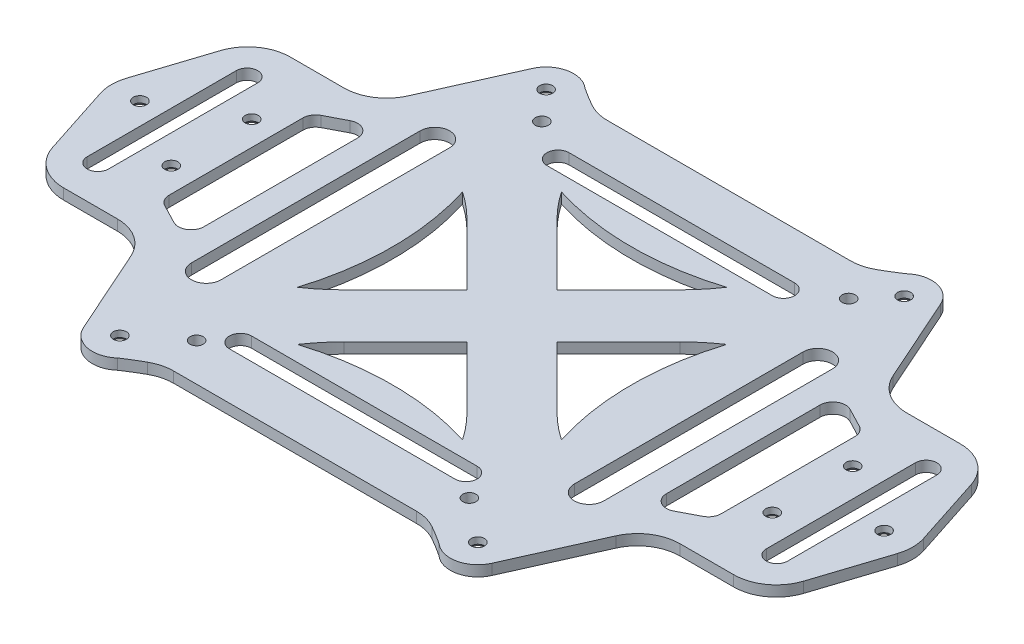
SolidWorks part; units mm, degrees
material "PPS"
ref_plane "前视基准面" through (0, 0, 0) normal (0, 0, 1) x (1, 0, 0)
ref_plane "上视基准面" through (0, 0, 0) normal (0, 1, 0) x (1, 0, 0)
ref_plane "右视基准面" through (0, 0, 0) normal (1, 0, 0) x (0, 0, -1)
sketch "参考" plane through (0, 0, 0) normal (0, 1, 0) x (1, 0, 0)
  line L3 (-133.7177, 0) -> (146.3754, 0) construction
  line L56 (0, 96.0639) -> (0, -115.1457) construction
  line L177 (114.5911, 7.4683) -> (114.5911, -7.4683)
  line L178 (114.5911, 7.4683) -> (43.1936, 17.6463)
  line L179 (114.5911, -7.4683) -> (43.1936, -17.6463)
  line L180 (-114.5911, -7.4683) -> (-43.1936, -17.6463)
  line L181 (-114.5911, 7.4683) -> (-114.5911, -7.4683)
  line L182 (-114.5911, 7.4683) -> (-43.1936, 17.6463)
  arc A18 (-37.7098, 54.831) -> (37.7098, 54.831) centre (0, 111.5317) ccw
  arc A20 (48.2756, 48.4632) -> (43.1936, 17.6463) centre (246.1791, 0) ccw
  arc A21 (48.2756, 48.4632) -> (37.7098, 54.831) centre (42, 50) ccw
  arc A22 (-37.7098, -54.831) -> (37.7098, -54.831) centre (0, -111.5317) cw
  arc A23 (48.2756, -48.4632) -> (43.1936, -17.6463) centre (246.1791, 0) cw
  arc A24 (48.2756, -48.4632) -> (37.7098, -54.831) centre (42, -50) cw
  arc A26 (-48.2756, -48.4632) -> (-37.7098, -54.831) centre (-42, -50) ccw
  arc A27 (-48.2756, -48.4632) -> (-43.1936, -17.6463) centre (-246.1791, 0) ccw
  arc A28 (-48.2756, 48.4632) -> (-37.7098, 54.831) centre (-42, 50) cw
  arc A30 (-48.2756, 48.4632) -> (-43.1936, 17.6463) centre (-246.1791, 0) cw
  dimension "D11" = 50
  dimension "D12" = 42
sketch "草图1" plane through (0, 0, 0) normal (0, 1, 0) x (1, 0, 0)
  line L0 (-160.1541, 0) -> (172.3115, 0) construction
  line L1 (0, 124.2182) -> (0, -143.4382) construction
  line L2 (79.6696, -17.5) -> (79.6696, 17.5) construction
  line L3 (77.1696, -17.5) -> (77.1696, 17.5)
  line L4 (82.1696, -17.5) -> (82.1696, 17.5)
  line L5 (-133.7177, 0) -> (146.3754, 0) construction
  line L6 (47.9, 52.6334) -> (59.525, 26.5883)
  line L7 (59.525, 26.5883) -> (85.8696, 26.5883)
  line L8 (85.8696, 26.5883) -> (94.5058, 0)
  line L9 (59.525, -26.5883) -> (85.8696, -26.5883)
  line L10 (47.9, -52.6334) -> (59.525, -26.5883)
  line L11 (85.8696, -26.5883) -> (94.5058, 0)
  line L12 (-47.9, -52.6334) -> (-59.525, -26.5883)
  line L13 (-59.525, -26.5883) -> (-85.8696, -26.5883)
  line L14 (-85.8696, -26.5883) -> (-94.5058, 0)
  line L15 (-85.8696, 26.5883) -> (-94.5058, 0)
  line L16 (-47.9, 52.6334) -> (-59.525, 26.5883)
  line L17 (-59.525, 26.5883) -> (-85.8696, 26.5883)
  line L18 (-79.6696, -17.5) -> (-79.6696, 17.5) construction
  line L19 (-77.1696, -17.5) -> (-77.1696, 17.5)
  line L20 (-82.1696, -17.5) -> (-82.1696, 17.5)
  line L21 (-24.996, 14.4296) -> (-10.5664, 0)
  line L22 (14.4296, 24.996) -> (0, 10.5664)
  line L23 (-24.996, -14.4296) -> (-10.5664, 0)
  line L24 (-14.4296, 24.996) -> (0, 10.5664)
  line L25 (0, 96.0639) -> (0, -115.1457) construction
  line L26 (24.996, -14.4296) -> (10.5664, 0)
  line L27 (24.996, 14.4296) -> (10.5664, 0)
  line L28 (-14.4296, -24.996) -> (0, -10.5664)
  line L29 (14.4296, -24.996) -> (0, -10.5664)
  line L30 (44.9192, -26.8293) -> (44.9192, 26.8293) construction
  line L31 (41.4687, -26.8293) -> (41.4687, 26.8293)
  line L32 (48.3697, -26.8293) -> (48.3697, 26.8293)
  line L33 (-26.4535, -37.2441) -> (26.4535, -37.2441) construction
  line L34 (-26.4535, -34.637) -> (26.4535, -34.637)
  line L35 (-26.4535, -39.8513) -> (26.4535, -39.8513)
  line L36 (-26.4535, 37.2441) -> (26.4535, 37.2441) construction
  line L37 (-26.4535, 34.637) -> (26.4535, 34.637)
  line L38 (-26.4535, 39.8513) -> (26.4535, 39.8513)
  line L39 (-44.9192, -26.8293) -> (-44.9192, 26.8293) construction
  line L40 (-41.4687, -26.8293) -> (-41.4687, 26.8293)
  line L41 (-48.3697, -26.8293) -> (-48.3697, 26.8293)
  line L42 (-30.9782, 50.8906) -> (30.9782, 50.8906)
  line L43 (-30.9782, -50.8906) -> (30.9782, -50.8906)
  circle A6 centre (42, 50) radius 1.55
  circle A7 centre (42, -50) radius 1.55
  circle A8 centre (-42, -50) radius 1.55
  circle A9 centre (-42, 50) radius 1.55
  circle A10 centre (36, 43) radius 1.55
  circle A11 centre (32, -42) radius 1.55
  circle A12 centre (-32, -42) radius 1.55
  circle A13 centre (-36, 43) radius 1.55
  arc A14 (47.9, 52.6334) -> (37.7098, 54.831) centre (42, 50) ccw
  arc A15 (-37.7098, 54.831) -> (-30.9782, 50.8906) centre (0, 111.5317) ccw
  arc A18 (77.1696, -17.5) -> (82.1696, -17.5) centre (79.6696, -17.5) ccw
  arc A19 (82.1696, 17.5) -> (77.1696, 17.5) centre (79.6696, 17.5) ccw
  circle A20 centre (70.5, 9.4358) radius 1.55
  circle A21 centre (70.5, -9.4358) radius 1.55
  circle A22 centre (-70.5, -9.4358) radius 1.55
  circle A23 centre (-70.5, 9.4358) radius 1.55
  circle A24 centre (87.3, 0) radius 1.55
  arc A25 (48.2756, 48.4632) -> (37.7098, 54.831) centre (42, 50) ccw construction
  arc A26 (47.9, -52.6334) -> (37.7098, -54.831) centre (42, -50) cw
  arc A27 (-37.7098, -54.831) -> (-30.9782, -50.8906) centre (0, -111.5317) cw
  arc A28 (-47.9, 52.6334) -> (-37.7098, 54.831) centre (-42, 50) cw
  arc A29 (-77.1696, -17.5) -> (-82.1696, -17.5) centre (-79.6696, -17.5) cw
  arc A30 (-82.1696, 17.5) -> (-77.1696, 17.5) centre (-79.6696, 17.5) cw
  circle A31 centre (-87.3, 0) radius 1.55
  arc A32 (-47.9, -52.6334) -> (-37.7098, -54.831) centre (-42, -50) ccw
  arc A33 (-24.996, 14.4296) -> (-30.9782, 19.3706) centre (-53.9062, -14.4807) ccw
  arc A34 (-24.996, -14.4296) -> (-30.9782, -19.3706) centre (-53.9062, 14.4807) cw
  arc A35 (-30.9782, -19.3706) -> (-30.9782, 19.3706) centre (-93.0146, 0) ccw
  arc A36 (-14.4296, 24.996) -> (-19.3706, 30.9782) centre (14.4807, 53.9062) cw
  arc A37 (-19.3706, 30.9782) -> (19.3706, 30.9782) centre (0, 93.0146) ccw
  arc A38 (14.4296, 24.996) -> (19.3706, 30.9782) centre (-14.4807, 53.9062) ccw
  arc A39 (24.996, 14.4296) -> (30.9782, 19.3706) centre (53.9062, -14.4807) cw
  arc A40 (30.9782, 19.3706) -> (30.9782, -19.3706) centre (93.0146, 0) ccw
  arc A41 (24.996, -14.4296) -> (30.9782, -19.3706) centre (53.9062, 14.4807) ccw
  arc A42 (14.4296, -24.996) -> (19.3706, -30.9782) centre (-14.4807, -53.9062) cw
  arc A43 (19.3706, -30.9782) -> (-19.3706, -30.9782) centre (0, -93.0146) ccw
  arc A44 (-14.4296, -24.996) -> (-19.3706, -30.9782) centre (14.4807, -53.9062) ccw
  arc A45 (41.4687, -26.8293) -> (48.3697, -26.8293) centre (44.9192, -26.8293) ccw
  arc A46 (48.3697, 26.8293) -> (41.4687, 26.8293) centre (44.9192, 26.8293) ccw
  arc A47 (-26.4535, -34.637) -> (-26.4535, -39.8513) centre (-26.4535, -37.2441) ccw
  arc A48 (26.4535, -39.8513) -> (26.4535, -34.637) centre (26.4535, -37.2441) ccw
  arc A49 (-26.4535, 34.637) -> (-26.4535, 39.8513) centre (-26.4535, 37.2441) cw
  arc A50 (26.4535, 39.8513) -> (26.4535, 34.637) centre (26.4535, 37.2441) cw
  arc A51 (-41.4687, -26.8293) -> (-48.3697, -26.8293) centre (-44.9192, -26.8293) cw
  arc A52 (-48.3697, 26.8293) -> (-41.4687, 26.8293) centre (-44.9192, 26.8293) cw
  arc A53 (30.9782, 50.8906) -> (37.7098, 54.831) centre (0, 111.5317) ccw
  arc A54 (30.9782, -50.8906) -> (37.7098, -54.831) centre (0, -111.5317) cw
  point P30 (79.6696, 0)
  point P63 (44.9192, 0)
  point P78 (-79.6696, 0)
  point P98 (0, 0)
  point P116 (0, -37.2441)
  point P129 (0, 37.2441)
  point P136 (-44.9192, 0)
  dimension "D1" = 50
  dimension "D3" = 3.1
  dimension "D8" = 2.5
  dimension "D10" = 3.1
  dimension "D12" = 3.1
  dimension "D2" = 42
  dimension "D4" = 36
  dimension "D5" = 32
  dimension "D6" = 42
  dimension "D7" = 43
  dimension "D9" = 35
  dimension "D11" = 70.5
  dimension "D13" = 87.3
  dimension "D14" = 4
extrude "凸台-拉伸1" add sketch "草图1" along normal blind 2.5
fillet "圆角1" radius 10 14 edges at (59.525, 1.25, -26.5883) (85.8696, 1.25, -26.5883) (85.8696, 1.25, 26.5883) (94.5058, 1.25, 0) (59.525, 1.25, 26.5883) (-59.525, 1.25, 26.5883) (-59.525, 1.25, -26.5883) (-85.8696, 1.25, -26.5883) (-85.8696, 1.25, 26.5883) (-94.5058, 1.25, 0) (30.9782, 1.25, -50.8906) (-30.9782, 1.25, -50.8906) (30.9782, 1.25, 50.8906) (-30.9782, 1.25, 50.8906)
chamfer "倒角2" distance 1 angle 45 10 edges at (-70.5, 0, 10.9858) (-70.5, 0, -10.9858) (70.5, 0, 7.8858) (70.5, 0, -7.8858) (-87.3, 0, -1.55) (87.3, 0, 1.55) (-42, 0, 51.55) (42, 0, 48.45) (-42, 0, -51.55) (42, 0, -48.45)
sketch "减重草图镂空-如果影响结构强度则取消" plane through (0, 0, 0) normal (0, -1, 0) x (1, 0, 0)
  line L0 (0, 0) -> (0, 77.9145) construction
  line L1 (0, 0) -> (127.571, 0) construction
  line L2 (-64.75, 17.5) -> (-54.25, 22.966)
  line L3 (-54.25, 22.966) -> (-54.25, -22.966)
  line L4 (-54.25, -22.966) -> (-64.75, -17.5)
  line L5 (-64.75, -17.5) -> (-64.75, 17.5)
  line L6 (54.25, -22.966) -> (64.75, -17.5)
  line L7 (54.25, 22.966) -> (54.25, -22.966)
  line L8 (64.75, 17.5) -> (54.25, 22.966)
  line L9 (64.75, -17.5) -> (64.75, 17.5)
  circle A1 centre (-70.5, 9.4358) radius 1.55 construction
  dimension "D1" = 5.75
  dimension "D2" = 54.25
  dimension "D3" = 62.5
  dimension "D4" = 17.5
extrude "减重-如果影响结构强度则取消" cut sketch "减重草图镂空-如果影响结构强度则取消" against normal through all
fillet "圆角2" radius 3 8 edges at (64.75, 1.25, 17.5) (64.75, 1.25, -17.5) (54.25, 1.25, -22.966) (54.25, 1.25, 22.966) (-54.25, 1.25, -22.966) (-64.75, 1.25, -17.5) (-64.75, 1.25, 17.5) (-54.25, 1.25, 22.966)
